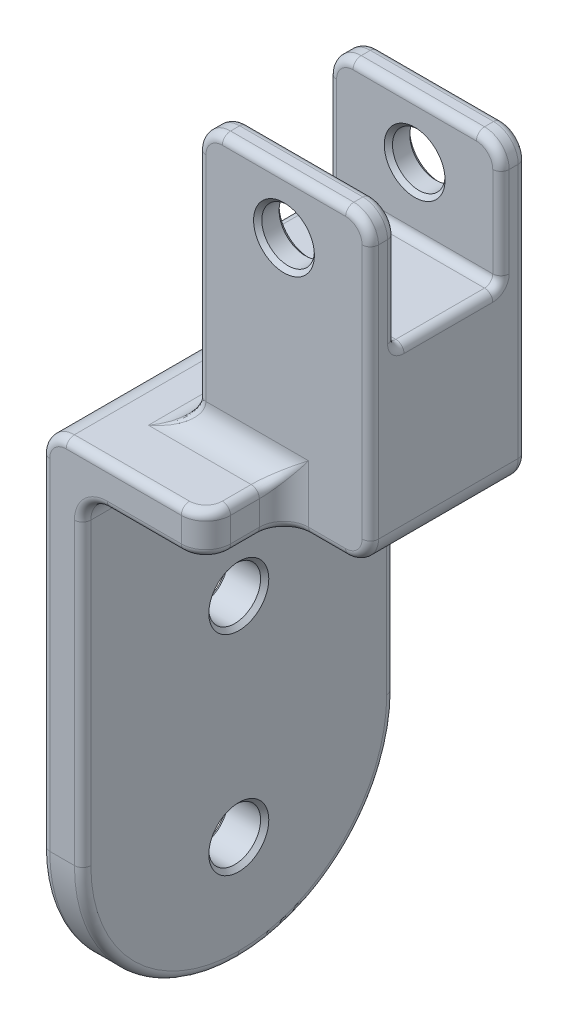
SolidWorks part; units mm, degrees
ref_plane "Front" through (0, 0, 0) normal (0, 0, 1) x (1, 0, 0)
ref_plane "Top" through (0, 0, 0) normal (0, 1, 0) x (1, 0, 0)
ref_plane "Right" through (0, 0, 0) normal (1, 0, 0) x (0, 0, -1)
ref_plane "Plane1" through (39.1342, 0, 0) normal (1, 0, 0) x (0, 0, -1)
sketch "Sketch1" plane through (39.1342, 0, 0) normal (1, 0, 0) x (0, 0, -1)
  line L0 (0, -40.64) -> (0, -117.14) construction
  line L1 (-19, -117.14) -> (19, -117.14)
  line L2 (19, -117.14) -> (19, -58.74)
  line L3 (19, -58.74) -> (-19, -58.74)
  line L4 (-10.6654, -117.14) -> (10.6654, -117.14) construction
  line L5 (10.6654, -117.14) -> (10.6654, -58.74) construction
  line L6 (-10.6654, -58.74) -> (-10.6654, -117.14) construction
  line L7 (10.6654, -22.59) -> (-10.6654, -22.59) construction
  line L8 (-10.6654, -58.74) -> (10.6654, -58.74) construction
  line L9 (10.6654, -58.74) -> (10.6654, -22.59) construction
  line L10 (-10.6654, -22.59) -> (-10.6654, -58.74) construction
  line L11 (-19, -58.74) -> (-19, -117.14)
  circle A3 centre (0, -104.14) radius 3.15
  circle A4 centre (0, -78.74) radius 3.15
  circle A5 centre (0, -40.64) radius 3.45 construction
  point P21 (0, -117.14)
  dimension "D1" = 6.3
  dimension "D2" = 6.3
  dimension "D4" = 25.4
  dimension "D5" = 38.1
  dimension "D3" = 20
  dimension "D6" = 13
  dimension "D7" = 38
extrude "TibiaMount" add sketch "Sketch1" along normal blind 5
sketch "Sketch2" plane through (0, 0, 0) normal (0, 0, 1) x (1, 0, 0)
  line L2 (39.1342, -58.74) -> (39.1342, -117.14) construction
  line L3 (44.1342, -58.74) -> (39.1342, -58.74)
  line L4 (44.1342, -58.74) -> (59.1342, -58.74)
  line L9 (44.1342, -58.74) -> (39.1342, -58.74) construction
  line L10 (44.1342, -58.74) -> (44.1342, -117.14) construction
  line L11 (39.1342, -58.74) -> (39.1342, -117.14) construction
  line L12 (44.1342, -117.14) -> (39.1342, -117.14) construction
  dimension "D1" = 20
extrude "ConnectingBridge" add sketch "Sketch2" along normal up to surface and the other way up to surface thin up to face at (41.6342, -87.94, 19) other way up to face at (41.6342, -87.94, -19) thin type one direction reverse wall 5
sketch "Sketch6" plane through (0, 0, 0) normal (0, 0, 1) x (1, 0, 0)
  line L0 (48.6342, -28.74) -> (59.1342, -28.74) construction
  line L1 (59.1342, -28.74) -> (59.1342, -58.74) construction
  line L2 (59.1342, -58.74) -> (48.6342, -58.74)
  line L3 (48.6342, -28.74) -> (48.6342, -21.74)
  line L4 (48.6342, -21.74) -> (69.6342, -21.74)
  line L5 (48.6342, -28.74) -> (48.6342, -58.74)
  line L6 (69.6342, -21.74) -> (69.6342, -58.74)
  line L7 (39.1342, -53.74) -> (39.1342, -117.14) construction
  line L8 (39.1342, -53.74) -> (39.1342, -117.14) construction
  line L9 (69.6342, -58.74) -> (59.1342, -58.74)
  circle A0 centre (59.1342, -28.74) radius 3.2
  dimension "D1" = 6.4
  dimension "D2" = 10.5
  dimension "D3" = 30
  dimension "D4" = 21
  dimension "D5" = 7
extrude "EndCap-Holder" add sketch "Sketch6" along normal mid plane 19 contours L2 L5 L3 L4 L6 L9 | A0
sketch "Sketch14" plane through (0, 0, 0) normal (0, 0, 1) x (1, 0, 0)
  point P0 (59.1342, -28.74)
  point P1 (0, 0)
  dimension "D1" = 28.74
  dimension "D2" = 59.1342
sketch "Sketch15" plane through (69.6342, 0, 0) normal (1, 0, 0) x (0, 0, -1)
  line L0 (-9.5, -21.74) -> (9.5, -21.74) construction
  line L1 (-6.4, -36.74) -> (6.4, -36.74)
  line L2 (-6.4, -36.74) -> (-6.4, -21.74)
  line L3 (-6.4, -21.74) -> (6.4, -21.74)
  line L4 (6.4, -36.74) -> (6.4, -21.74)
  line L5 (-6.4, -36.74) -> (6.4, -21.74) construction
  line L6 (-6.4, -21.74) -> (6.4, -36.74) construction
  line L7 (0, -29.24) -> (0, 0) construction
  point P0 (0, -29.24)
  dimension "D1" = 12.8
  dimension "D2" = 15
extrude "EndCap-notch" cut sketch "Sketch15" against normal up to next
chamfer "Chamfer0.5" distance 0.5 angle 45 8 edges at (39.1342, -100.99, 0) (44.1342, -100.99, 0) (39.1342, -75.59, 0) (44.1342, -75.59, 0) (62.3342, -28.74, -9.5) (55.9342, -28.74, -6.4) (62.3342, -28.74, 9.5) (62.3342, -28.74, 6.4)
fillet "Fillet-3.0" radius 3 14 edges at (59.1342, -56.24, 19) (59.1342, -56.24, -19) (39.1342, -53.74, 0) (53.8842, -53.74, -9.5) (53.8842, -53.74, 9.5) (48.6342, -53.74, 0) (59.1342, -56.24, 9.5) (59.1342, -56.24, -9.5) (48.6342, -21.74, 7.95) (48.6342, -21.74, -7.95) (69.6342, -21.74, -7.95) (69.6342, -21.74, 7.95) (44.1342, -58.74, 0) (69.6342, -58.74, 0)
fillet "Fillet-19.0" radius 19 2 edges at (41.6342, -117.14, 19) (41.6342, -117.14, -19)
fillet "Fillet-1.0" radius 1 58 edges at (59.1342, -21.74, -6.4) (49.5128, -22.6187, -6.4) (68.7555, -22.6187, -6.4) (48.6342, -30.74, -6.4) (69.6342, -30.74, -6.4) (48.6342, -36.74, 0) (69.6342, -36.74, 0) (48.6342, -30.74, 6.4) (49.5128, -22.6187, 6.4) (69.6342, -30.74, 6.4) (68.7555, -22.6187, 6.4) (47.7555, -52.8613, -10.3787) (48.6342, -37.74, -9.5) (49.5128, -22.6187, -9.5) (59.1342, -21.74, -9.5) (68.7555, -22.6187, -9.5) (69.6342, -40.24, -9.5) (68.7555, -57.8613, -9.5) (64.3842, -58.74, -9.5) (60.0128, -58.74, -10.3787) (59.1342, -58.74, -14.25) (58.2555, -58.74, -18.1213) (47.7555, -52.8613, 10.3787) (48.6342, -37.74, 9.5) (49.5128, -22.6187, 9.5) (59.1342, -21.74, 9.5) (68.7555, -22.6187, 9.5) (69.6342, -40.24, 9.5) (68.7555, -57.8613, 9.5) (64.3842, -58.74, 9.5) (60.0128, -58.74, 10.3787) (59.1342, -58.74, 14.25) (58.2555, -58.74, 18.1213) (51.6342, -58.74, 19) (45.0128, -59.6187, 19) (44.1342, -79.94, 19) (44.1342, -111.575, 13.435) (44.1342, -111.575, -13.435) (44.1342, -79.94, -19) (45.0128, -59.6187, -19) (60.0128, -52.8613, -10.3787) (60.0128, -52.8613, 10.3787) (59.1342, -53.74, 14.25) (58.2555, -53.74, 18.1213) (49.1342, -53.74, 19) (40.0128, -54.6187, 19) (39.1342, -77.44, 19) (39.1342, -111.575, 13.435) (39.1342, -111.575, -13.435) (39.1342, -77.44, -19) (40.0128, -54.6187, -19) (49.1342, -53.74, -19) (58.2555, -53.74, -18.1213) (59.1342, -36.74, -6.4) (59.1342, -36.74, 6.4) (59.1342, -21.74, 6.4) (51.6342, -58.74, -19) (59.1342, -53.74, -14.25)
equation "\"D2@Sketch1\"=\"D1@Sketch1\""
equation "\"D4@Sketch6\"=\"D2@Sketch6\"*2"
